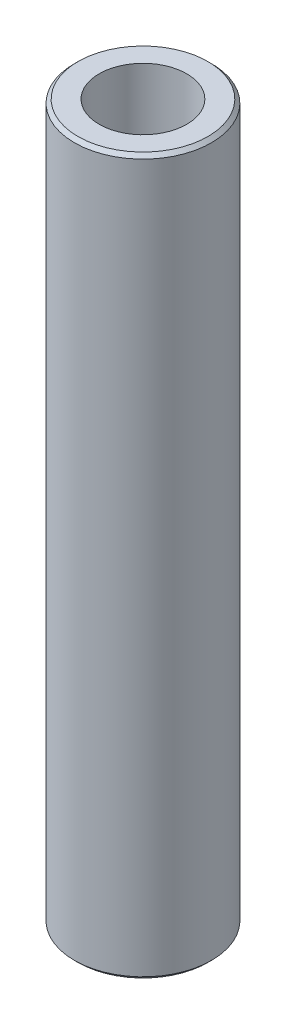
SolidWorks part; units mm, degrees
ref_plane "Front Plane" through (0, 0, 0) normal (0, 0, 1) x (1, 0, 0)
ref_plane "Top Plane" through (0, 0, 0) normal (0, 1, 0) x (1, 0, 0)
ref_plane "Right Plane" through (0, 0, 0) normal (1, 0, 0) x (0, 0, -1)
sketch "Sketch1" plane through (0, 0, 0) normal (0, 1, 0) x (1, 0, 0)
  circle A0 centre (0, 0) radius 57.5
  dimension "SHAFT_OD" = 115
extrude "Boss-Extrude1" add sketch "Sketch1" along normal blind 600
sketch "Sketch2" plane through (0, 0, 0) normal (0, 1, 0) x (1, 0, 0)
  circle A0 centre (0, 0) radius 36.7354
  dimension "BORE_D" = 73.4708
extrude "Cut-Extrude1" cut sketch "Sketch2" along normal through all
chamfer "Chamfer1" distance 3.0103 angle 45 2 edges at (0, 600, 57.5) (0, 0, 57.5)
